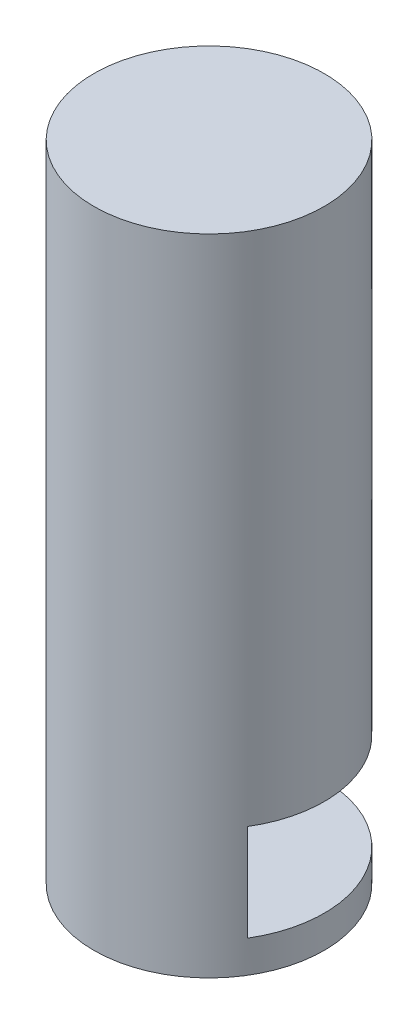
SolidWorks part; units mm, degrees
ref_plane "Front Plane" through (0, 0, 0) normal (0, 0, 1) x (1, 0, 0)
ref_plane "Top Plane" through (0, 0, 0) normal (0, 1, 0) x (1, 0, 0)
ref_plane "Right Plane" through (0, 0, 0) normal (1, 0, 0) x (0, 0, -1)
sketch "Sketch1" plane through (0, 0, 0) normal (0, 1, 0) x (1, 0, 0)
  circle A0 centre (0, 0) radius 7.15
extrude "Boss-Extrude1" add sketch "Sketch1" along normal blind 40
sketch "Sketch2" plane through (0, 0, 0) normal (0, -1, 0) x (1, 0, 0)
  circle A0 centre (0, 0) radius 1
extrude "Cut-Extrude1" cut sketch "Sketch2" against normal blind 4
ref_plane "Plane1" through (0, 2, 0) normal (0, 1, 0) x (1, 0, 0)
sketch "Sketch3" plane through (0, 2, 0) normal (0, 1, 0) x (1, 0, 0)
  line L1 (-7.5477, 7.488) -> (7.5876, 7.488)
  line L2 (-7.5477, 7.488) -> (-7.5477, -3.7241)
  line L3 (-7.5477, -3.7241) -> (7.5876, -3.7241)
  line L4 (7.5876, 7.488) -> (7.5876, -3.7241)
extrude "Cut-Extrude2" cut sketch "Sketch3" along normal blind 6
sketch "Sketch4" plane through (0, -2, 0) normal (0, -1, 0) x (1, 0, 0)
  circle A0 centre (0, 0) radius 1 construction
  circle A1 centre (0, 0) radius 1
